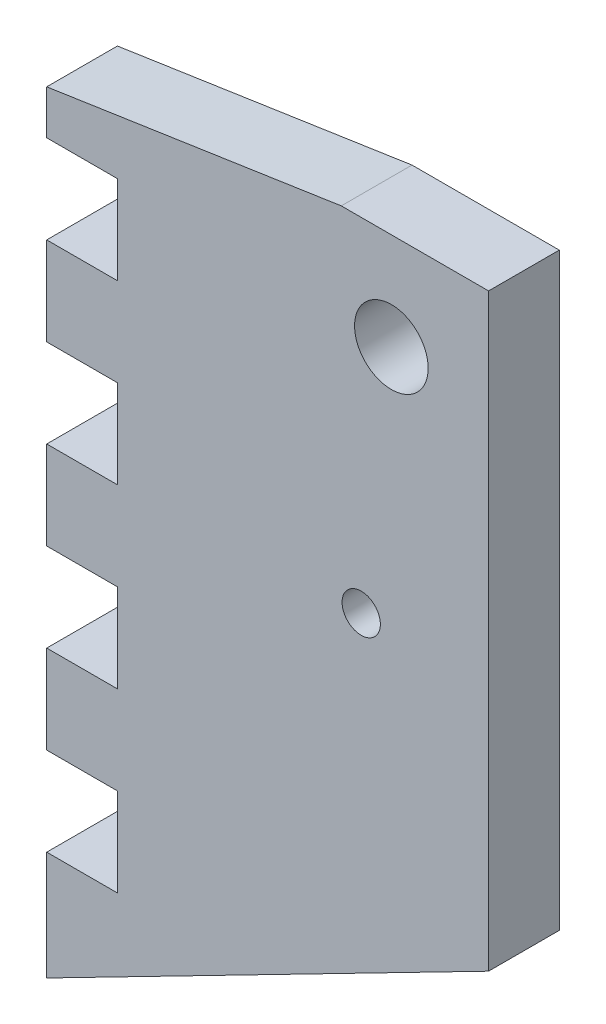
SolidWorks part; units mm, degrees
material "Thornel VCB-20 Carbon Cloth"
ref_plane "Front Plane" through (0, 0, 0) normal (0, 0, 1) x (1, 0, 0)
ref_plane "Top Plane" through (0, 0, 0) normal (0, 1, 0) x (1, 0, 0)
ref_plane "Right Plane" through (0, 0, 0) normal (1, 0, 0) x (0, 0, -1)
sketch "Sketch1" plane through (0, 0, 0) normal (0, 0, 1) x (1, 0, 0)
  line L0 (0, 0) -> (-38.1, 0)
  line L1 (0, 0) -> (0, -50.8)
  line L2 (-38.1, 0) -> (-38.1, -7.62)
  line L3 (-38.1, -7.62) -> (-32.004, -7.62)
  line L4 (-32.004, -7.62) -> (-32.004, -15.24)
  line L5 (-32.004, -15.24) -> (-38.1, -15.24)
  line L6 (-38.1, -45.72) -> (-38.1, -70.358)
  line L7 (-38.1, -15.24) -> (-38.1, -22.86)
  line L8 (-38.1, -22.86) -> (-32.004, -22.86)
  line L9 (-32.004, -22.86) -> (-32.004, -30.48)
  line L10 (-32.004, -30.48) -> (-38.1, -30.48)
  line L11 (-38.1, -30.48) -> (-38.1, -38.1)
  line L12 (-38.1, -38.1) -> (-32.004, -38.1)
  line L13 (-32.004, -38.1) -> (-32.004, -45.72)
  line L14 (-32.004, -45.72) -> (-38.1, -45.72)
  line L15 (-38.1, -70.358) -> (0, -50.8)
  circle A0 centre (-8.382, -8.382) radius 3.175
  dimension "D9" = 6.35
  dimension "D1" = 38.1
  dimension "D2" = 50.8
  dimension "D3" = 7.62
  dimension "D4" = 7.62
  dimension "D6" = 6.096
  dimension "D8" = 70.358
  dimension "D12" = 8.382
  dimension "D13" = 8.382
  dimension "D7" = 3
extrude "Boss-Extrude1" add sketch "Sketch1" along normal blind 6.096 contours L6 L15 L1 L0 L2 L3 L4 L5 L7 L8 L9 L10 L11 L12 L13 L14 A0 region at (-19.2717, -31.1343, 0)
sketch "Sketch2" plane through (0, 0, 0) normal (0, 0, -1) x (-1, 0, 0)
  line L5 (38.1, 0) -> (12.7, 0)
  line L6 (0, 0) -> (38.1, 0) construction
  line L7 (12.7, 0) -> (38.1, -3.81)
  line L8 (38.1, 0) -> (38.1, -7.62) construction
  line L9 (38.1, -3.81) -> (38.1, 0)
  dimension "D1" = 25.4
  dimension "D2" = 3.81
extrude "Cut-Extrude1" cut sketch "Sketch2" against normal blind 8.636
sketch "Sketch4" plane through (0, 0, 6.096) normal (0, 0, 1) x (1, 0, 0)
  line L0 (-38.1, -45.72) -> (-38.1, -53.34)
  line L1 (-38.1, -45.72) -> (-38.1, -70.358) construction
  line L2 (-38.1, -53.34) -> (-32.004, -53.34)
  line L3 (-32.004, -53.34) -> (-32.004, -60.96)
  line L4 (-32.004, -60.96) -> (-38.1, -60.96)
  line L5 (-38.1, -60.96) -> (-38.1, -53.34)
  line M18 (-38.1, -45.72) -> (-38.1, -70.358)
  dimension "D1" = 7.62
  dimension "D2" = 6.096
  dimension "D3" = 6.096
  dimension "D4" = 7.62
extrude "Cut-Extrude2" cut sketch "Sketch4" against normal through all contours L4 L3 L2 M18 region at (-35.052, -57.15, 6.096)
sketch "Sketch5" plane through (0, 0, 0) normal (0, 0, -1) x (-1, 0, 0)
  line L0 (8.382, -8.382) -> (10.9822, -29.559) construction
  line L1 (8.382, -8.382) -> (8.382, -39.2411) construction
  circle A0 centre (8.382, -8.382) radius 3.175 construction
  circle A1 centre (10.9822, -29.559) radius 1.651
  dimension "D1" = 21.336
  dimension "D2" = 7
extrude "Cut-Extrude4" cut sketch "Sketch5" against normal up to surface (6.096 mm away) up to face at (-5.207, -8.382, 6.096)
